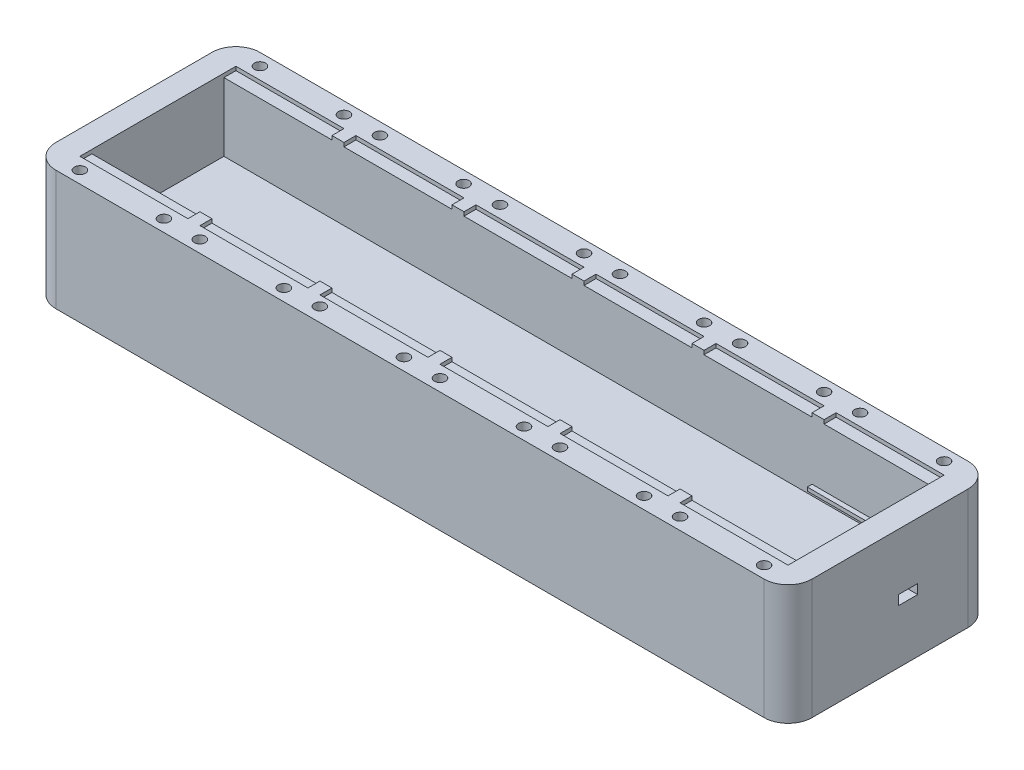
SolidWorks part; units mm, degrees
ref_plane "Ebene vorne" through (0, 0, 0) normal (0, 0, 1) x (1, 0, 0)
ref_plane "Ebene oben" through (0, 0, 0) normal (0, 1, 0) x (1, 0, 0)
ref_plane "Ebene rechts" through (0, 0, 0) normal (1, 0, 0) x (0, 0, -1)
sketch "Skizze2" plane through (0, 0, 0) normal (0, 0, 1) x (1, 0, 0)
  line L1 (0, 0) -> (315, 0)
  line L2 (0, 0) -> (0, 50)
  line L3 (0, 50) -> (315, 50)
  line L4 (315, 0) -> (315, 50)
  dimension "D1" = 315
  dimension "D2" = 50
extrude "Aufsatz-Linear austragen1" add sketch "Skizze2" along normal blind 85
sketch "Skizze4" plane through (0, 50, 0) normal (0, 1, 0) x (1, 0, 0)
  line L0 (315, 0) -> (0, 0) construction
  line L1 (10, -15) -> (305, -15)
  line L2 (10, -15) -> (10, -70)
  line L3 (10, -70) -> (305, -70)
  line L4 (305, -15) -> (305, -70)
  line L5 (315, -85) -> (0, -85) construction
  line L6 (0, -85) -> (0, 0) construction
  line L7 (315, -85) -> (315, 0) construction
  dimension "D1" = 15
  dimension "D2" = 15
  dimension "D3" = 10
  dimension "D4" = 10
extrude "Schnitt-Linear austragen1" cut sketch "Skizze4" against normal blind 30
fillet "Verrundung1" radius 10 1 edges at (315, 25, 0)
fillet "Verrundung2" radius 10 1 edges at (315, 25, 85)
fillet "Verrundung3" radius 10 1 edges at (0, 25, 85)
fillet "Verrundung4" radius 10 1 edges at (0, 25, 0)
sketch "Skizze11" plane through (0, 50, 0) normal (0, 1, 0) x (1, 0, 0)
  line L0 (10, -70) -> (305, -70) construction
  line L1 (10, -15) -> (55, -15)
  line L2 (10, -15) -> (10, -10)
  line L3 (10, -10) -> (55, -10)
  line L4 (55, -15) -> (55, -10)
  line L5 (55, -70) -> (10, -70)
  line L6 (55, -70) -> (55, -75)
  line L7 (55, -75) -> (10, -75)
  line L8 (10, -70) -> (10, -75)
  line L9 (305, -15) -> (10, -15) construction
  line L10 (60, -75) -> (105, -75)
  line L11 (60, -75) -> (60, -70)
  line L12 (60, -70) -> (105, -70)
  line L13 (105, -75) -> (105, -70)
  line L14 (110, -75.0087) -> (155, -75.0087)
  line L15 (110, -75.0087) -> (110, -70)
  line L16 (110, -70) -> (155, -70)
  line L17 (155, -75.0087) -> (155, -70)
  line L18 (160, -75.0087) -> (205, -75.0087)
  line L19 (160, -75.0087) -> (160, -70)
  line L20 (160, -70) -> (205, -70)
  line L21 (205, -75.0087) -> (205, -70)
  line L22 (210, -75) -> (255, -75)
  line L23 (210, -75) -> (210, -70)
  line L24 (210, -70) -> (255, -70)
  line L25 (255, -75) -> (255, -70)
  line L26 (260, -75) -> (305, -75)
  line L27 (260, -75) -> (260, -70)
  line L28 (260, -70) -> (305, -70)
  line L29 (305, -75) -> (305, -70)
  line L30 (305, -15) -> (260, -15)
  line L31 (305, -15) -> (305, -10)
  line L32 (305, -10) -> (260, -10)
  line L33 (260, -15) -> (260, -10)
  line L35 (255, -15) -> (210, -15)
  line L36 (255, -15) -> (255, -10)
  line L37 (255, -10) -> (210, -10)
  line L38 (210, -15) -> (210, -10)
  line L39 (205, -15) -> (160, -15)
  line L40 (205, -15) -> (205, -10)
  line L41 (205, -10) -> (160, -10)
  line L42 (160, -15) -> (160, -10)
  line L43 (155, -15) -> (110, -15)
  line L44 (155, -15) -> (155, -10)
  line L45 (155, -10) -> (110, -10)
  line L46 (110, -15) -> (110, -10)
  line L47 (105, -15) -> (60, -15)
  line L48 (105, -15) -> (105, -10)
  line L49 (105, -10) -> (60, -10)
  line L50 (60, -15) -> (60, -10)
  dimension "D1" = 45
  dimension "D2" = 5
  dimension "D3" = 45
  dimension "D4" = 5
  dimension "D5" = 5
  dimension "D6" = 5
  dimension "D7" = 5
  dimension "D8" = 5
  dimension "D9" = 5
  dimension "D10" = 45
  dimension "D11" = 45
  dimension "D12" = 45
  dimension "D13" = 45
  dimension "D14" = 45
  dimension "D15" = 5
  dimension "D16" = 5
  dimension "D17" = 5
  dimension "D18" = 5
  dimension "D19" = 45
  dimension "D20" = 45
  dimension "D21" = 45
  dimension "D22" = 45
  dimension "D23" = 5
  dimension "D24" = 5
  dimension "D25" = 5
  dimension "D26" = 5
  dimension "D27" = 5
  dimension "D28" = 5
  dimension "D29" = 5
  dimension "D30" = 5
extrude "Schnitt-Linear austragen4" cut sketch "Skizze11" against normal blind 1.6
sketch "Skizze13" plane through (0, 20, 0) normal (0, 1, 0) x (1, 0, 0)
  line L0 (10, -15) -> (10, -70) construction
  line L1 (305, -70) -> (10, -70)
  line L2 (305, -70) -> (305, -67)
  line L3 (305, -67) -> (10, -67)
  line L4 (10, -70) -> (10, -67)
  line L5 (305, -15) -> (10, -15) construction
  dimension "D1" = 52
extrude "Aufsatz-Linear austragen2" add sketch "Skizze13" along normal blind 4.2
sketch "Skizze14" plane through (305, 0, 0) normal (-1, 0, 0) x (0, 0, 1)
  line L0 (15, 20) -> (15, 48.4) construction
  line L1 (31, 26.4) -> (39, 26.4)
  line L2 (31, 26.4) -> (31, 22.4)
  line L3 (31, 22.4) -> (39, 22.4)
  line L4 (39, 26.4) -> (39, 22.4)
  line L5 (67, 20) -> (15, 20) construction
  dimension "D1" = 8
  dimension "D2" = 4
  dimension "D3" = 16
  dimension "D4" = 2.4
extrude "Schnitt-Linear austragen5" cut sketch "Skizze14" against normal blind 19
sketch "Skizze15" plane through (0, 0, 15) normal (0, 0, 1) x (1, 0, 0)
  line L0 (305, 20) -> (305, 48.4) construction
  line L1 (305, 22.7) -> (255, 22.7)
  line L2 (305, 22.7) -> (305, 24.2)
  line L3 (305, 24.2) -> (255, 24.2)
  line L4 (255, 22.7) -> (255, 24.2)
  line L5 (305, 20) -> (10, 20) construction
  dimension "D1" = 50
  dimension "D2" = 1.5
  dimension "D3" = 2.7
extrude "Aufsatz-Linear austragen3" add sketch "Skizze15" along normal blind 2
sketch "Skizze16" plane through (0, 0, 67) normal (0, 0, -1) x (-1, 0, 0)
  line L1 (-305, 24.2) -> (-255, 24.2)
  line L2 (-305, 24.2) -> (-305, 22.7)
  line L3 (-305, 22.7) -> (-255, 22.7)
  line L4 (-255, 24.2) -> (-255, 22.7)
  dimension "D1" = 50
  dimension "D2" = 1.5
extrude "Aufsatz-Linear austragen4" add sketch "Skizze16" along normal blind 2
sketch "Skizze17" plane through (0, 50, 0) normal (0, 1, 0) x (1, 0, 0)
  line L0 (55, -75) -> (55, -70) construction
  line L1 (305, 0) -> (10, 0) construction
  line L2 (305, -85) -> (10, -85) construction
  line L3 (10, -70) -> (10, -75) construction
  line L4 (10, -10) -> (10, -75) construction
  line L5 (55, -15) -> (55, -10) construction
  line L6 (60, -70) -> (60, -75) construction
  line L7 (105, -75) -> (105, -70) construction
  line L8 (155, -75.0087) -> (155, -70) construction
  line L10 (160, -70) -> (160, -75.0087) construction
  line L11 (205, -75.0087) -> (205, -70) construction
  line L12 (305, -75) -> (305, -10) construction
  line L13 (260, -70) -> (260, -75) construction
  line L14 (255, -75) -> (255, -70) construction
  line L15 (210, -70) -> (210, -75) construction
  line L16 (60, -10) -> (60, -15) construction
  line L18 (110, -10) -> (110, -15) construction
  circle A0 centre (50, -80) radius 2.3
  circle A1 centre (15, -80) radius 2.3
  circle A2 centre (15, -5) radius 2.3
  circle A3 centre (50, -5) radius 2.3
  circle A4 centre (65, -5) radius 2.3
  circle A5 centre (99.8349, -5) radius 2.3
  circle A6 centre (65, -80) radius 2.3
  circle A7 centre (100, -80) radius 2.3
  circle A8 centre (114.1455, -79.164) radius 2.3
  circle A9 centre (150, -80) radius 2.3
  circle A10 centre (165, -80) radius 2.3
  circle A11 centre (200, -80) radius 2.3
  circle A12 centre (215, -80) radius 2.3
  circle A13 centre (250, -80) radius 2.3
  circle A14 centre (265, -80) radius 2.3
  circle A15 centre (300, -80) radius 2.3
  circle A16 centre (300, -5) radius 2.3
  circle A17 centre (265, -5) radius 2.3
  circle A18 centre (250, -5) radius 2.3
  circle A19 centre (215, -5) radius 2.3
  circle A20 centre (200, -5) radius 2.3
  circle A21 centre (165, -5) radius 2.3
  circle A22 centre (150, -5) radius 2.3
  circle A23 centre (115, -5) radius 2.3
  dimension "D1" = 4.6
  dimension "D2" = 4.6
  dimension "D3" = 4.6
  dimension "D4" = 4.6
  dimension "D5" = 5
  dimension "D6" = 5
  dimension "D7" = 5
  dimension "D8" = 5
  dimension "D10" = 5
  dimension "D11" = 5
  dimension "D12" = 5
  dimension "D13" = 4.6
  dimension "D14" = 4.6
  dimension "D15" = 4.6
  dimension "D16" = 4.6
  dimension "D17" = 4.6
  dimension "D18" = 4.6
  dimension "D19" = 4.6
  dimension "D20" = 4.6
  dimension "D21" = 4.6
  dimension "D22" = 4.6
  dimension "D23" = 5
  dimension "D25" = 5
  dimension "D26" = 5
  dimension "D27" = 5
  dimension "D28" = 5
  dimension "D29" = 5
  dimension "D30" = 5
  dimension "D31" = 5
  dimension "D32" = 5
  dimension "D33" = 5
  dimension "D34" = 5
  dimension "D35" = 5
  dimension "D36" = 5
  dimension "D37" = 5
  dimension "D38" = 5
  dimension "D39" = 5
  dimension "D40" = 5
  dimension "D41" = 5
  dimension "D42" = 5
  dimension "D43" = 4.6
  dimension "D44" = 4.6
  dimension "D45" = 4.6
  dimension "D46" = 4.6
  dimension "D47" = 4.6
  dimension "D48" = 4.6
  dimension "D49" = 4.6
  dimension "D50" = 4.6
  dimension "D51" = 4.6
  dimension "D52" = 4.6
  dimension "D53" = 5
  dimension "D54" = 5
  dimension "D9" = 5
  dimension "D24" = 5
extrude "Schnitt-Linear austragen6" cut sketch "Skizze17" against normal blind 4
sketch "Skizze19" plane through (0, 50, 0) normal (0, 1, 0) x (1, 0, 0)
  line L0 (305, -85) -> (10, -85) construction
  line L1 (157.5, -85) -> (340.3, -85)
  line L2 (157.5, -85) -> (157.5, 0)
  line L3 (157.5, 0) -> (340.3, 0)
  line L4 (340.3, -85) -> (340.3, 0)
